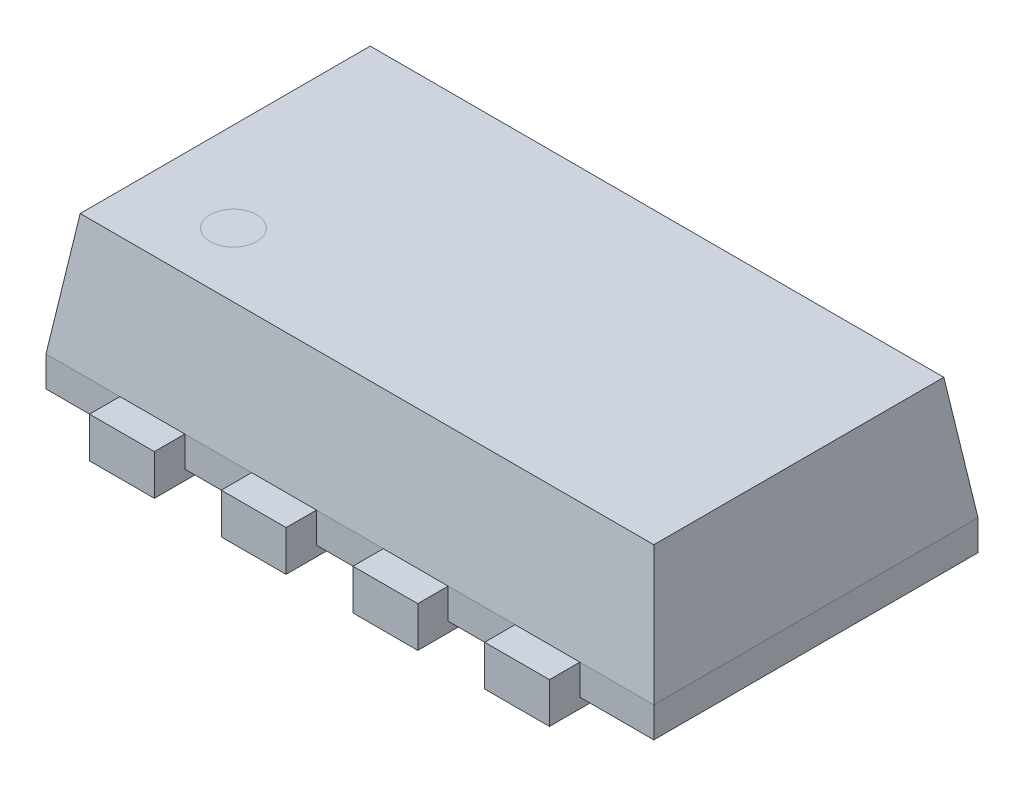
SolidWorks part; units mm, degrees
ref_plane "Спереди" through (0, 0, 0) normal (0, 0, 1) x (1, 0, 0)
ref_plane "Сверху" through (0, 0, 0) normal (0, 1, 0) x (1, 0, 0)
ref_plane "Справа" through (0, 0, 0) normal (1, 0, 0) x (0, 0, -1)
sketch "Эскиз1" plane through (0, 0, 0) normal (0, 1, 0) x (1, 0, 0)
  line L1 (-1.5, -0.8) -> (1.5, -0.8)
  line L2 (-1.5, -0.8) -> (-1.5, 0.8)
  line L3 (-1.5, 0.8) -> (1.5, 0.8)
  line L4 (1.5, -0.8) -> (1.5, 0.8)
  line L5 (-1.5, -0.8) -> (1.5, 0.8) construction
  line L6 (-1.5, 0.8) -> (1.5, -0.8) construction
  point P0 (0, 0)
  dimension "D1" = 3
  dimension "D2" = 1.6
extrude "Бобышка-Вытянуть1" add sketch "Эскиз1" along normal blind 0.15 from offset 0.05
sketch "Эскиз2" plane through (0, 0, 0) normal (0, 1, 0) x (1, 0, 0)
  line L1 (1.5, 0.8) -> (-1.5, 0.8)
  line L2 (1.5, 0.8) -> (1.5, -0.8)
  line L3 (1.5, -0.8) -> (-1.5, -0.8)
  line L4 (-1.5, 0.8) -> (-1.5, -0.8)
  line L5 (1.5, 0.8) -> (-1.5, -0.8) construction
  line L6 (1.5, -0.8) -> (-1.5, 0.8) construction
  point P0 (0, 0)
extrude "Бобышка-Вытянуть2" add sketch "Эскиз2" along normal blind 0.6 draft 8 from offset 0.2
sketch "Эскиз4" plane through (0, 0, 0) normal (0, 1, 0) x (1, 0, 0)
  line L0 (0, 0) -> (-1.6112, 0) construction
  line L1 (0, 0) -> (0, 1.0039) construction
  line L2 (-0.975, 0) -> (-0.975, 1.1435) construction
  line L3 (-0.815, -0.67) -> (-0.815, -0.95)
  line L4 (-1.135, 0.67) -> (-0.815, 0.67)
  line L5 (-1.135, 0.67) -> (-1.135, 0.95)
  line L6 (-1.135, 0.95) -> (-0.815, 0.95)
  line L7 (-0.815, 0.67) -> (-0.815, 0.95)
  line L8 (-1.135, 0.67) -> (-0.815, 0.95) construction
  line L9 (-1.135, 0.95) -> (-0.815, 0.67) construction
  line L10 (-1.135, -0.67) -> (-0.815, -0.67)
  line L11 (-1.135, -0.95) -> (-0.815, -0.95)
  line L12 (-1.135, -0.67) -> (-1.135, -0.95)
  point P6 (-0.975, 0.81)
  dimension "D1" = 0.975
  dimension "D2" = 0.28
  dimension "D3" = 0.32
  dimension "D4" = 0.95
extrude "Бобышка-Вытянуть3" add sketch "Эскиз4" along normal blind 0.2 separate body
pattern_linear "Линейный массив1" count 4 spacing 0.65 along (1, 0, 0) of "Бобышка-Вытянуть3"
sketch "Эскиз5" plane through (0, 0.8, 0) normal (0, 1, 0) x (1, 0, 0)
  line L0 (-0.975, -0.95) -> (-0.975, 0.15) construction
  line L1 (-1.135, -0.95) -> (-0.815, -0.95) construction
  line L2 (0, 0) -> (-1.5765, 0) construction
  line L3 (-0.975, -0.4) -> (-1.6176, -0.4) construction
  circle A0 centre (-0.975, -0.4) radius 0.115
  dimension "D1" = 0.23
  dimension "D2" = 0.4
extrude "Вырез-Вытянуть1" cut sketch "Эскиз5" against normal blind 0.01
extrude "Бобышка-Вытянуть4" add sketch "Эскиз5<2>" against normal blind 0.01 separate body
sketch "Эскиз5<2>" plane through (0, 0.8, 0) normal (0, 1, 0) x (1, 0, 0) same geometry as "Эскиз5"
